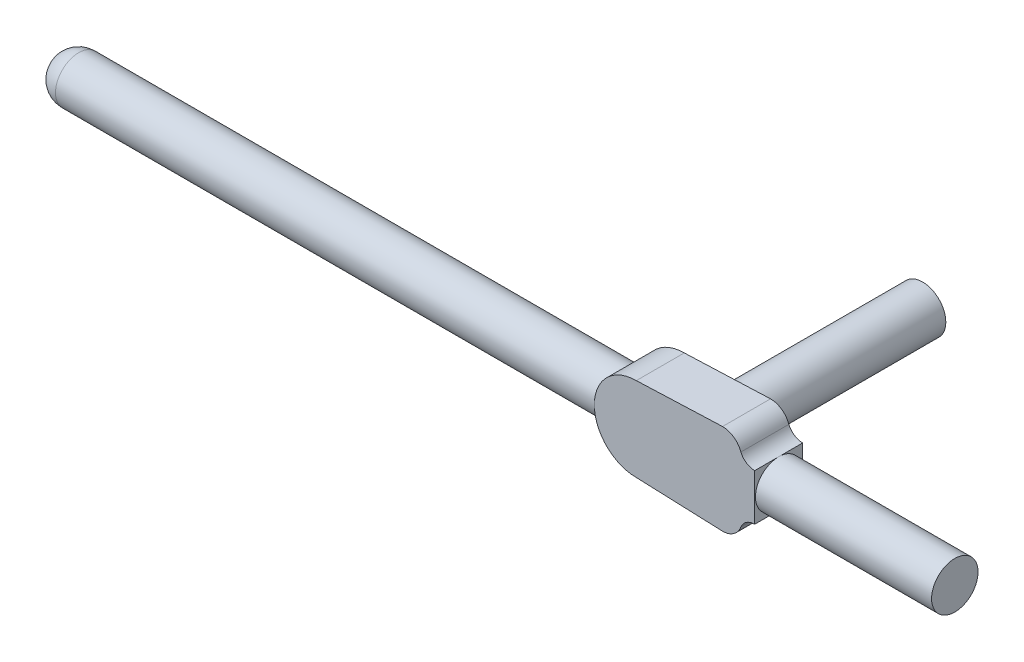
SolidWorks part; units mm, degrees
ref_plane "Alzado" through (0, 0, 0) normal (0, 0, 1) x (1, 0, 0)
ref_plane "Planta" through (0, 0, 0) normal (0, 1, 0) x (1, 0, 0)
ref_plane "Vista lateral" through (0, 0, 0) normal (1, 0, 0) x (0, 0, -1)
sketch "Croquis1" plane through (0, 0, 0) normal (0, 0, 1) x (1, 0, 0)
  line L0 (0, 359.1368) -> (0, -481.9187) construction
  line L1 (-657.792, 0) -> (755.6133, 0) construction
  line L3 (-300, 0) -> (300, 0)
  line L5 (-284.5, 15.5) -> (300, 15.5)
  line L6 (300, 0) -> (300, 15.5)
  arc A2 (-300, 0) -> (-284.5, 15.5) centre (-284.5, 0) cw
  dimension "D3" = 600
  dimension "D2" = 300
  dimension "D1" = 15.5
revolve "Revolución1" add sketch "Croquis1" angle 360 about L1
sketch "Croquis3" plane through (0, 0, 0) normal (0, 0, 1) x (1, 0, 0)
  line L0 (75.5, 87.2879) -> (75.5, -75.7996) construction
  line L1 (-284.5, 15.5) -> (-284.5, -15.5) construction
  line L2 (182.5, 79.0968) -> (182.5, -79.9585) construction
  line L3 (275.34, 0) -> (-79.3359, 0) construction
  line L4 (161.0396, 30.25) -> (161.0396, -30.25) construction
  line L5 (103.5, 28) -> (103.5, -28) construction
  line L7 (103.5, -28) -> (161.0396, -30.25)
  line L8 (103.5, 28) -> (161.0396, 30.25)
  line L9 (-284.5, -15.5) -> (300, -15.5) construction
  line L10 (-284.5, -15.5) -> (300, -15.5)
  line L11 (182.5, 15.5) -> (182.5, -15.5)
  arc A0 (173.2816, -21.6243) -> (182.5, -15.5) centre (182.5, -25.5) cw
  arc A1 (161.0396, -30.25) -> (173.2816, -21.6243) centre (161.0396, -17.25) ccw
  arc A2 (103.5, -28) -> (103.5, 28) centre (103.5, 0) cw
  arc A3 (173.2816, 21.6243) -> (182.5, 15.5) centre (182.5, 25.5) ccw
  arc A4 (161.0396, 30.25) -> (173.2816, 21.6243) centre (161.0396, 17.25) cw
  point P11 (161.0396, 0)
  point P14 (103.5, 0)
  dimension "D5" = 10
  dimension "D6" = 13
  dimension "D8" = 28
  dimension "D1" = 360
  dimension "D2" = 107
  dimension "D3" = 56
  dimension "D4" = 60.5
  dimension "D7" = 21.4604
extrude "Saliente-Extruir1" add sketch "Croquis3" along normal mid plane 32 contours A4 L8 A2 L10 L11 A3 | A2 L7 A1 A0 L10 region at (131.1824, -21.9003, 0) region at (130.1192, 5.7219, 0)
sketch "Croquis4" plane through (0, 0, -16) normal (0, 0, -1) x (-1, 0, 0)
  line L0 (51.5528, 0) -> (-321.594, 0) construction
  line L1 (-145, 52.3215) -> (-145, -43.2699)
  line L2 (-300, 15.5) -> (-300, -15.5) construction
  circle A0 centre (-129.5, 0) radius 15.5
  dimension "D2" = 31
  dimension "D1" = 155
extrude "Saliente-Extruir2" add sketch "Croquis4" along normal blind 133 contours A0 L0 | L0 A0 region at (129.5, -6.5784, -16) region at (129.5, 6.5784, -16)
